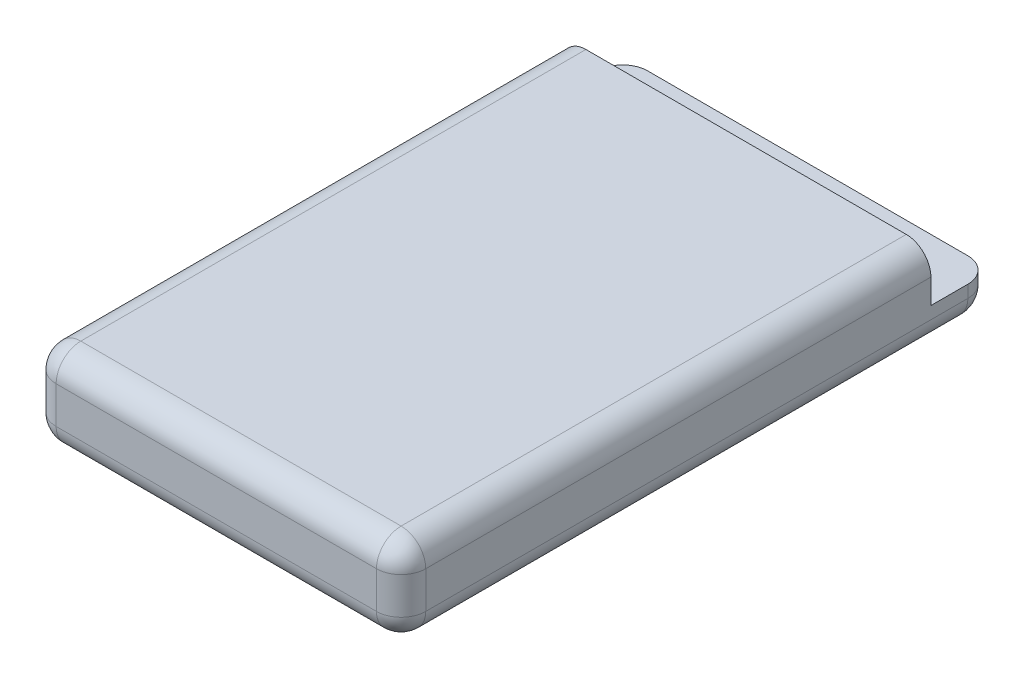
SolidWorks part; units mm, degrees
ref_plane "Спереди" through (0, 0, 0) normal (0, 0, 1) x (1, 0, 0)
ref_plane "Сверху" through (0, 0, 0) normal (0, 1, 0) x (1, 0, 0)
ref_plane "Справа" through (0, 0, 0) normal (1, 0, 0) x (0, 0, -1)
sketch "Эскиз1" plane through (0, 0, 0) normal (0, 1, 0) x (1, 0, 0)
  line L1 (-15, -24) -> (15, -24)
  line L2 (-15, -24) -> (-15, 24)
  line L3 (-15, 24) -> (15, 24)
  line L4 (15, -24) -> (15, 24)
  line L5 (-15, -24) -> (15, 24) construction
  line L6 (-15, 24) -> (15, -24) construction
  point P0 (0, 0)
  dimension "D1" = 48
  dimension "D2" = 30
extrude "Бобышка-Вытянуть1" add sketch "Эскиз1" along normal blind 7
fillet "Скругление1" radius 2 8 edges at (0, 0, -24) (-15, 0, 0) (0, 0, 24) (15, 0, 0) (0, 7, 24) (-15, 7, 0) (0, 7, -24) (15, 7, 0)
fillet "Скругление2" radius 2 12 edges at (14.4142, 6.4142, -23.4142) (14.4142, 0.5858, -23.4142) (14.4142, 6.4142, 23.4142) (14.4142, 0.5858, 23.4142) (-14.4142, 6.4142, -23.4142) (-14.4142, 0.5858, -23.4142) (-14.4142, 6.4142, 23.4142) (-14.4142, 0.5858, 23.4142) (15, 3.5, -24) (15, 3.5, 24) (-15, 3.5, -24) (-15, 3.5, 24)
sketch "Эскиз2" plane through (0, 7, 0) normal (0, 1, 0) x (1, 0, 0)
  line L1 (-15.5748, 24) -> (18.279, 24)
  line L2 (-15.5748, 24) -> (-15.5748, 19)
  line L3 (-15.5748, 19) -> (18.279, 19)
  line L4 (18.279, 24) -> (18.279, 19)
  line L5 (-13, 24) -> (13, 24) construction
  line L6 (-13, 24) -> (13, 24)
  line M5 (-13, 22) -> (-13, -22)
  line M7 (13, -22) -> (13, 22)
  line M8 (13, 22) -> (-13, 22)
  dimension "D1" = 5
extrude "Вырез-Вытянуть1" cut sketch "Эскиз2" against normal blind 4 contours L3 M5 M7 M8 | L4 L1 L2 L3 M5 M8 M7 region at (2.5076, 7, -22.3546) region at (0, 7, -20.5)
ref_plane "Плоскость1" through (13, -4.5, 21.4169) normal (0, 0, -1) x (-1, 0, 0)
sketch "Эскиз5" plane through (0, -4.5, 0) normal (0, -1, 0) x (1, 0, 0)
  line L0 (4.578, -4.5831) -> (4.578, -15.6614)
  line L1 (1, -4.5831) -> (-13, -4.5831) construction
  line L2 (4.578, -15.6614) -> (-13, -15.6614)
  line L3 (-13, 22) -> (-13, -22) construction
  line L4 (-13, -15.6614) -> (-13, -7.7638)
  line L5 (-13, -7.7638) -> (1.1861, -7.7638)
  line L6 (1.1861, -7.7638) -> (1.1861, -4.5831)
  line L7 (1.1861, -4.5831) -> (4.578, -4.5831)
